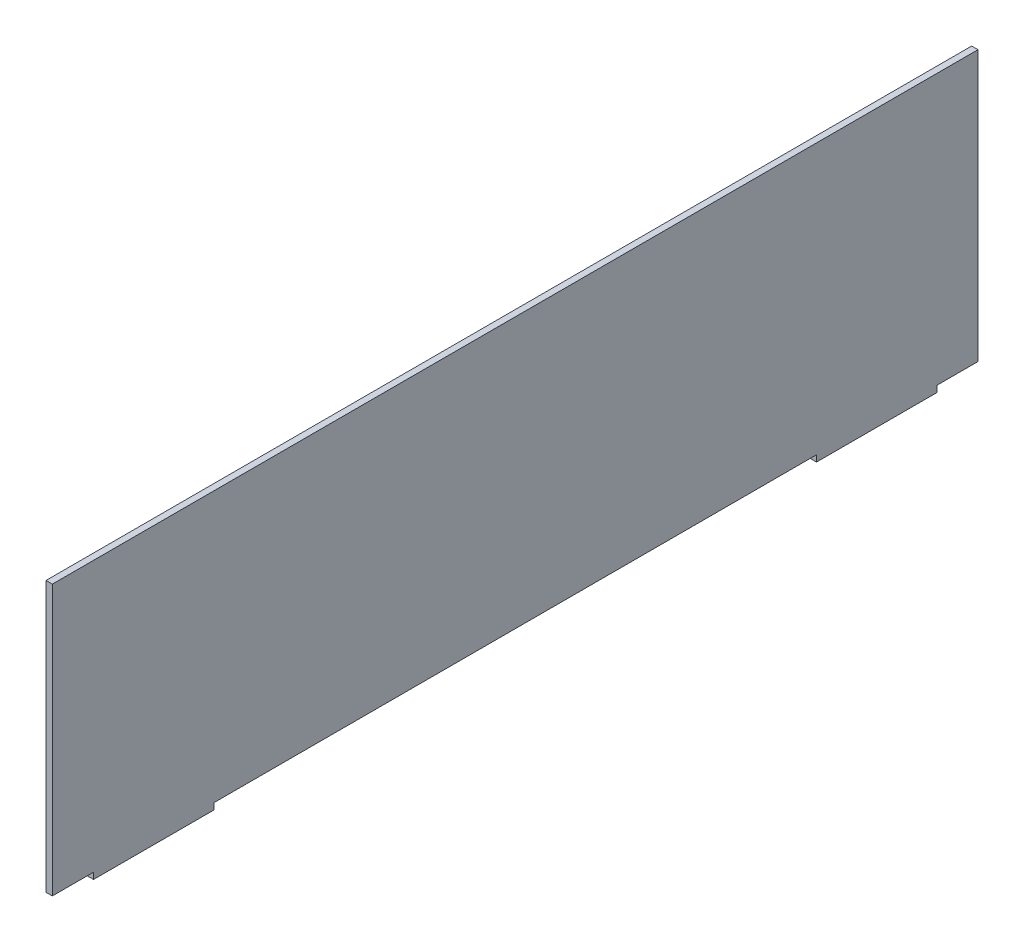
SolidWorks part; units mm, degrees
material "Custom Plastic"
ref_plane "X-Y Datum" through (0, 0, 0) normal (0, 0, 1) x (1, 0, 0)
ref_plane "X-Z Datum" through (0, 0, 0) normal (0, 1, 0) x (1, 0, 0)
ref_plane "Y-Z Datum" through (0, 0, 0) normal (1, 0, 0) x (0, 0, -1)
sketch "Sketch1" plane through (0, 0, 0) normal (1, 0, 0) x (0, 0, -1)
  line L1 (-232.0925, 67.7228) -> (232.0925, 67.7228)
  line L2 (-232.0925, 67.7228) -> (-232.0925, -67.7228)
  line L3 (-232.0925, -67.7228) -> (232.0925, -67.7228)
  line L4 (232.0925, 67.7228) -> (232.0925, -67.7228)
  line L5 (-232.0925, 67.7228) -> (232.0925, -67.7228) construction
  line L6 (-232.0925, -67.7228) -> (232.0925, 67.7228) construction
  point P0 (0, 0)
  dimension "D1" = 464.185
  dimension "D2" = 135.4455
sketch "Sketch2" plane through (0, 0, 0) normal (1, 0, 0) x (0, 0, -1)
  line L0 (-211.455, -67.7228) -> (-211.455, -70.8978)
  line L1 (-232.0925, -67.7228) -> (232.0925, -67.7228) construction
  line L2 (-211.455, -70.8978) -> (-151.13, -70.8977)
  line L3 (-151.13, -70.8977) -> (-151.13, -67.7228)
  line L4 (0, 55) -> (0, -55) construction
  line L5 (151.13, -70.8977) -> (151.13, -67.7228)
  line L6 (211.455, -70.8978) -> (151.13, -70.8977)
  line L7 (211.455, -67.7228) -> (211.455, -70.8978)
  line L8 (-211.455, -67.7228) -> (-151.13, -67.7228)
  line L9 (151.13, -67.7228) -> (211.455, -67.7228)
  point P4 (-181.2925, -70.8978)
  dimension "D1" = 3.175
  dimension "D2" = 60.325
  dimension "D3" = 50.8
base flange "Base-Flange1" sketch "Sketch1" thickness 3.175 reverse thickness direction no parameters "D1"=1
extrude "Boss-Extrude2" add sketch "Sketch2" against normal blind 3.175
sketch "Bend-Lines1" [suppressed] plane through (0, 0, 0) normal (0, 1, 0) x (1, 0, 0)
sketch "Bounding-Box1" [suppressed] plane through (0, 0, 0) normal (0, 1, 0) x (1, 0, 0)
sheet metal parameters "Sheet-Metal1" thickness 3.175 parameters "D1"=1
flat pattern "Flat-Pattern1" [suppressed]
sketch "Bend-Lines2" plane through (0, 0, 0) normal (0, 1, 0) x (1, 0, 0)
sketch3d "Bounding-Box2" [suppressed]
  line L0 (-232.0925, -69.3102, 0) -> (232.0925, -69.3102, 0) construction
  line L1 (-232.0925, 69.3103, 0) -> (232.0925, 69.3103, 0) construction
  line L2 (-232.0925, -69.3102, 0) -> (-232.0925, 69.3103, 0) construction
  line L3 (232.0925, -69.3102, 0) -> (232.0925, 69.3103, 0) construction
sheet metal parameters "Sheet-Metal7" thickness 3.175 parameters "D1"=1
flat pattern "Flat-Pattern1"
sketch "Bend-Lines2" plane through (0, 0, 0) normal (0, 1, 0) x (1, 0, 0)
sketch3d "Bounding-Box2" [suppressed]
  line L0 (-232.0925, -70.8978, 0) -> (232.0925, -70.8978, 0) construction
  line L1 (-232.0925, 67.7228, 0) -> (232.0925, 67.7228, 0) construction
  line L2 (-232.0925, -70.8978, 0) -> (-232.0925, 67.7228, 0) construction
  line L3 (232.0925, -70.8978, 0) -> (232.0925, 67.7228, 0) construction
